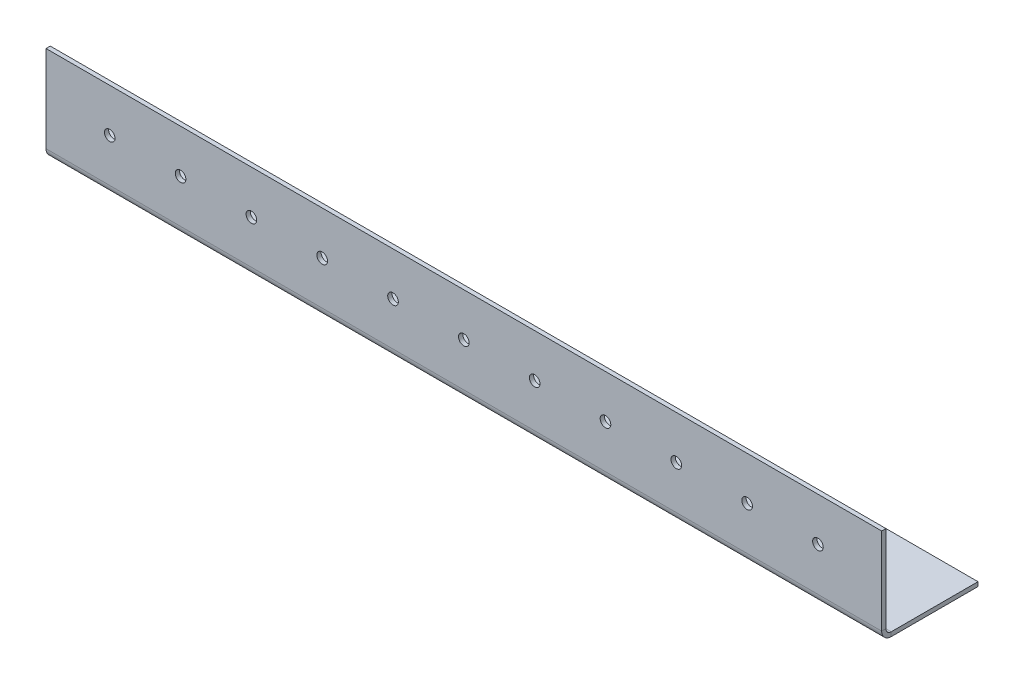
SolidWorks part; units mm, degrees
note: The reader was unsure of these and kept them because the rebuilt part matched: flange length of "Edge-Flange1".
material "AISI 1020"
ref_plane "Front Plane" through (0, 0, 0) normal (0, 0, 1) x (1, 0, 0)
ref_plane "Top Plane" through (0, 0, 0) normal (0, 1, 0) x (1, 0, 0)
ref_plane "Right Plane" through (0, 0, 0) normal (1, 0, 0) x (0, 0, -1)
sketch "Sketch1" plane through (0, 0, 0) normal (0, 1, 0) x (1, 0, 0)
  line L0 (-118, 26) -> (-118, 0)
  line L1 (-118, 26) -> (118, 26)
  line L2 (-118, 0) -> (118, 0)
  line L3 (118, 26) -> (118, 0)
  line L4 (-118, 26) -> (118, 0) construction
  line L5 (-118, 0) -> (118, 26) construction
  line L6 (0, 0) -> (59.8055, 0) construction
  point P1 (0, 13)
  dimension "D1" = 26
  dimension "D2" = 236
base flange "Base-Flange1" sketch "Sketch1" thickness 1.2 reverse thickness direction no parameters "D1"=0.7366
edge flange "Edge-Flange1" sketch "Sketch8" flange angle 90 flange length 26 flange position material outside bend radius 1.5 thickness 1.2 relief rectangular parameters "D6"=10
sketch "Sketch8" plane through (0, 0, 0) normal (0, 0, 1) x (1, 0, 0)
  line L2 (-118, 0) -> (-118, 26)
  line L3 (-118, 26) -> (118, 26)
  line L4 (118, 26) -> (118, 0)
  line L7 (-118, 0) -> (118, 0) construction
  line L8 (-118, 0) -> (118, 0)
bend "EdgeBend1" bend radius 1.5 bend angle 90 parameters "D5"=1
sketch "Sketch9" plane through (0, -1.2, 0) normal (0, -1, 0) x (1, 0, 0)
  line L0 (-118, -13.75) -> (118, -13.75) construction
  line L1 (-118, -26) -> (-118, -1.5) construction
  line L2 (118, -1.5) -> (118, -26) construction
  line L3 (-100, -13.75) -> (-80, -13.75) construction
  circle A0 centre (-100, -13.75) radius 1.5
  circle A1 centre (-80, -13.75) radius 1.5
  circle A2 centre (-60, -13.75) radius 1.5
  circle A3 centre (-40, -13.75) radius 1.5
  circle A4 centre (-20, -13.75) radius 1.5
  circle A5 centre (0, -13.75) radius 1.5
  circle A6 centre (20, -13.75) radius 1.5
  circle A7 centre (40, -13.75) radius 1.5
  circle A8 centre (60, -13.75) radius 1.5
  circle A9 centre (80, -13.75) radius 1.5
  circle A10 centre (100, -13.75) radius 1.5
  dimension "D1" = 3
  dimension "D2" = 18
  dimension "D4" = 20
  dimension "D3" = 11
extrude "Cut-Extrude1" cut sketch "Sketch9" against normal blind 10 normal cut yes
sketch "Sketch10" plane through (0, 0, 1.2) normal (0, 0, 1) x (1, 0, 0)
  line L0 (-118, 13.75) -> (118, 13.75) construction
  line L1 (-118, 26) -> (-118, 1.5) construction
  line L2 (118, 1.5) -> (118, 26) construction
  line L3 (-100, 13.75) -> (-80, 13.75) construction
  circle A0 centre (-100, 13.75) radius 1.5
  circle A1 centre (-80, 13.75) radius 1.5
  circle A2 centre (-60, 13.75) radius 1.5
  circle A3 centre (-40, 13.75) radius 1.5
  circle A4 centre (-20, 13.75) radius 1.5
  circle A5 centre (0, 13.75) radius 1.5
  circle A6 centre (20, 13.75) radius 1.5
  circle A7 centre (40, 13.75) radius 1.5
  circle A8 centre (60, 13.75) radius 1.5
  circle A9 centre (80, 13.75) radius 1.5
  circle A10 centre (100, 13.75) radius 1.5
  dimension "D1" = 3
  dimension "D2" = 18
  dimension "D4" = 20
  dimension "D3" = 11
extrude "Cut-Extrude2" cut sketch "Sketch10" against normal blind 10 normal cut yes
sketch "Bend-Lines1" [suppressed] plane through (0, 0, 0) normal (0, 1, 0) x (1, 0, 0)
sketch "Bounding-Box1" [suppressed] plane through (0, 0, 0) normal (0, 1, 0) x (1, 0, 0)
sheet metal parameters "Sheet-Metal1" thickness 1.2 parameters "D1"=0.7366
flat pattern "Flat-Pattern1" [suppressed]
sketch "Bend-Lines2" plane through (0, 0, 0) normal (0, 1, 0) x (1, 0, 0)
sketch3d "Bounding-Box2" [suppressed]
  line L0 (-118, 33, 0) -> (118, 33, 0) construction
  line L1 (-118, 0, 0) -> (118, 0, 0) construction
  line L2 (-118, 33, 0) -> (-118, 0, 0) construction
  line L3 (118, 33, 0) -> (118, 0, 0) construction
sheet metal parameters "Sheet-Metal2" thickness 1.2 parameters "D1"=0.7366
flat pattern "Flat-Pattern1"
sketch "Bend-Lines2" plane through (0, 0, 0) normal (0, 1, 0) x (1, 0, 0)
  line L0 (-118, 1.3) -> (118, 1.3) construction
  line L1 (-118, 1.3) -> (118, 1.3) construction
sketch3d "Bounding-Box2" [suppressed]
  line L0 (118, 26, 0) -> (-118, 26, 0) construction
  line L1 (118, -23.4, 0) -> (-118, -23.4, 0) construction
  line L2 (118, 26, 0) -> (118, -23.4, 0) construction
  line L3 (-118, 26, 0) -> (-118, -23.4, 0) construction
bend of the flat pattern "Flatten-<EdgeBend1>1"
sheet metal parameters "Sheet-Metal3" thickness 1.2 parameters "D1"=0.7366
flat pattern "Flat-Pattern1"
sketch "Bend-Lines2" plane through (0, 0, 0) normal (0, 1, 0) x (1, 0, 0)
  line L0 (-118, 1.3) -> (118, 1.3) construction
  line L1 (-118, 1.3) -> (118, 1.3) construction
sketch3d "Bounding-Box2" [suppressed]
  line L0 (118, 26, 0) -> (-118, 26, 0) construction
  line L1 (118, -23.4, 0) -> (-118, -23.4, 0) construction
  line L2 (118, 26, 0) -> (118, -23.4, 0) construction
  line L3 (-118, 26, 0) -> (-118, -23.4, 0) construction
bend of the flat pattern "Flatten-<EdgeBend1>1"
sheet metal parameters "Sheet-Metal4" thickness 1.2 parameters "D1"=0.7366
flat pattern "Flat-Pattern1"
sketch "Bend-Lines2" plane through (0, 0, 0) normal (0, 1, 0) x (1, 0, 0)
  line L0 (-118, 1.3) -> (118, 1.3) construction
  line L1 (-118, 1.3) -> (118, 1.3) construction
sketch3d "Bounding-Box2" [suppressed]
  line L0 (118, 26, 0) -> (-118, 26, 0) construction
  line L1 (118, -23.4, 0) -> (-118, -23.4, 0) construction
  line L2 (118, 26, 0) -> (118, -23.4, 0) construction
  line L3 (-118, 26, 0) -> (-118, -23.4, 0) construction
bend of the flat pattern "Flatten-<EdgeBend1>1"
